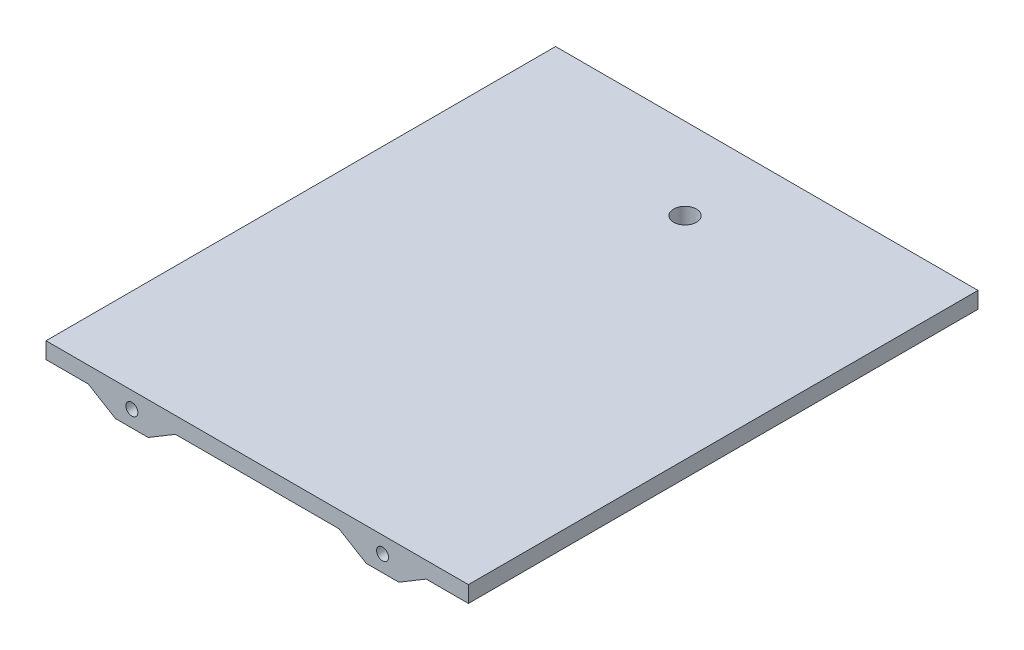
SolidWorks part; units mm, degrees
ref_plane "Płaszczyzna przednia" through (0, 0, 0) normal (0, 0, 1) x (1, 0, 0)
ref_plane "Płaszczyzna górna" through (0, 0, 0) normal (0, 1, 0) x (1, 0, 0)
ref_plane "Płaszczyzna prawa" through (0, 0, 0) normal (1, 0, 0) x (0, 0, -1)
sketch "Szkic15" plane through (0, 0, 0) normal (0, 1, 0) x (1, 0, 0)
  line L0 (-38.75, 69.3124) -> (38.75, 69.3124)
  line L1 (-38.75, 69.3124) -> (-38.75, -26.1876)
  line L2 (-38.75, -26.1876) -> (-52, -43.75)
  line L3 (38.75, 69.3124) -> (38.75, -26.1876)
  line L4 (38.75, -26.1876) -> (52, -43.75)
  line L5 (52, -74.75) -> (52, -43.75)
  line L6 (-60, -74.75) -> (60, -74.75)
  line L7 (-52, -43.75) -> (-52, -74.75)
  line L8 (35.7524, -27.1876) -> (38.75, -26.1876)
  line L9 (-38.75, -26.1876) -> (-35.75, -27.1876)
  line L10 (-35.75, -27.1876) -> (35.7524, -27.1876)
  line L11 (-38.75, -24.1876) -> (38.75, -24.1876)
  point P14 (0, 0)
  point P15 (0, 0)
  point P16 (0, 0)
  point P17 (0, 0)
  point P18 (0, 0)
  point P19 (0, 0)
  dimension "D1" = 3
  dimension "D3" = 77.5
  dimension "D4" = 22
  dimension "D5" = 31
  dimension "D6" = 93.5
  dimension "D7" = 2
  dimension "D8" = 2
  dimension "D9" = 3.16
  dimension "D10" = 3.1623
extrude "Dodanie-wyciągnięcie12" add sketch "Szkic15" along normal blind 3 contours L1 L11 L3 L0 region at (0, 0, -22.5624)
sketch "Szkic17" plane through (0, 0, 0) normal (0, -1, 0) x (1, 0, 0)
  line L1 (-4.5, -49.8124) -> (4.5, -49.8124)
  line L2 (-4.5, -49.8124) -> (-4.5, -58.8124)
  line L3 (-4.5, -58.8124) -> (4.5, -58.8124)
  line L4 (4.5, -49.8124) -> (4.5, -58.8124)
  line L5 (-15, -9.3124) -> (15, -9.3124)
  line L6 (-15, -9.3124) -> (-15, -39.3124)
  line L8 (15, -9.3124) -> (15, -39.3124)
  line L9 (-30, -39.3124) -> (-15, -39.3124)
  line L10 (-30, -39.3124) -> (-30, -69.3124)
  line L11 (-30, -69.3124) -> (-18.1323, -69.3124)
  line L12 (30, -39.3124) -> (30, -69.3124)
  line L13 (15, -69.3124) -> (30, -69.3124)
  line L15 (15, -39.3124) -> (30, -39.3124)
  line L16 (0, -49.8124) -> (0, 33.7148) construction
  line L17 (0, 33.7148) -> (0, -58.8124) construction
  line L18 (-4.5, -54.3124) -> (-57.4, -54.3124) construction
  line L21 (-18.1323, -69.3124) -> (15, -69.3124)
  line L22 (-38.75, -69.3124) -> (38.75, -69.3124) construction
  line L24 (38.75, -69.3124) -> (38.75, 24.1876) construction
  line L25 (-38.75, -69.3124) -> (-38.75, 24.1876) construction
  point P19 (0, 33.7148)
  dimension "D1" = 30
  dimension "D2" = 9
  dimension "D3" = 30
  dimension "D4" = 15
  dimension "D5" = 30
extrude "Dodanie-wyciągnięcie15" add sketch "Szkic17" along normal blind 3
sketch "Szkic18" plane through (0, -3, 0) normal (0, -1, 0) x (1, 0, 0)
  line L12 (-15, -9.3124) -> (-15, -39.3124)
  line L13 (-15, -39.3124) -> (-30, -39.3124)
  line L14 (-30, -39.3124) -> (-30, -69.3124)
  line L15 (-30, -69.3124) -> (30, -69.3124)
  line L20 (30, -69.3124) -> (30, -39.3124)
  line L21 (30, -39.3124) -> (15, -39.3124)
  line L22 (15, -39.3124) -> (15, -9.3124)
  line L23 (15, -9.3124) -> (-15, -9.3124)
  line L24 (-15, -9.3124) -> (-15, -39.3124)
  line L25 (-15, -39.3124) -> (-30, -39.3124)
  line L26 (-30, -39.3124) -> (-30, -69.3124)
  line L27 (-30, -69.3124) -> (30, -69.3124)
  line L32 (30, -69.3124) -> (30, -39.3124)
  line L33 (30, -39.3124) -> (15, -39.3124)
  line L34 (15, -39.3124) -> (15, -9.3124)
  line L35 (15, -9.3124) -> (-15, -9.3124)
  dimension "D1" = 0
extrude "Dodanie-wyciągnięcie16" add sketch "Szkic18" along normal blind 3
sketch "Szkic22" plane through (0, 3, 0) normal (0, 1, 0) x (1, 0, 0)
  line L4 (-4.5, 49.8124) -> (4.5, 49.8124)
  line L5 (4.5, 49.8124) -> (4.5, 58.8124)
  line L6 (4.5, 58.8124) -> (-4.5, 58.8124)
  line L7 (-4.5, 58.8124) -> (-4.5, 49.8124)
  line L8 (-4.5, 49.8124) -> (4.5, 49.8124)
  line L9 (4.5, 49.8124) -> (4.5, 58.8124)
  line L10 (4.5, 58.8124) -> (-4.5, 58.8124)
  line L11 (-4.5, 58.8124) -> (-4.5, 49.8124)
  line L18 (15, 69.3124) -> (-18.1323, 69.3124)
  line L19 (15, 69.3124) -> (-18.1323, 69.3124)
  line L23 (30, 69.3124) -> (15, 69.3124)
  line L24 (30, 39.3124) -> (30, 69.3124)
  line L25 (15, 39.3124) -> (30, 39.3124)
  line L26 (15, 9.3124) -> (15, 39.3124)
  line L27 (-15, 9.3124) -> (15, 9.3124)
  line L28 (-15, 39.3124) -> (-15, 9.3124)
  line L29 (-30, 39.3124) -> (-15, 39.3124)
  line L30 (-30, 69.3124) -> (-30, 39.3124)
  line L31 (-18.1323, 69.3124) -> (-30, 69.3124)
  line L35 (30, 69.3124) -> (15, 69.3124)
  line L36 (30, 39.3124) -> (30, 69.3124)
  line L37 (15, 39.3124) -> (30, 39.3124)
  line L38 (15, 9.3124) -> (15, 39.3124)
  line L39 (-15, 9.3124) -> (15, 9.3124)
  line L40 (-15, 39.3124) -> (-15, 9.3124)
  line L41 (-30, 39.3124) -> (-15, 39.3124)
  line L42 (-30, 69.3124) -> (-30, 39.3124)
  line L43 (-18.1323, 69.3124) -> (-30, 69.3124)
  circle A0 centre (0, 54.3124) radius 2.1
  point P10 (0, 49.8124)
  point P13 (4.5, 54.3124)
  dimension "D3" = 4.2
  dimension "D1" = 0
  dimension "D2" = 0
extrude "Wytnij-wyciągnięcie10" cut sketch "Szkic22" against normal blind 0.5 contours A0 region at (0, 3, -54.3124)
sketch "Szkic27" plane through (0, 0, 24.1876) normal (0, 0, 1) x (1, 0, 0)
  line L0 (-26, 3) -> (-20, 3)
  line L2 (-26, -3) -> (-20, -3)
  line L4 (-20, -3) -> (-20, 3)
  line L5 (-38.75, 3) -> (-38.75, 0) construction
  line L6 (0, -3) -> (0, 3) construction
  line L7 (-26, 3) -> (-20, 3)
  line L8 (38.75, 3) -> (38.75, 0) construction
  line L9 (-38.75, 3) -> (38.75, 3) construction
  line L10 (-26, 3) -> (-26, -3)
  line L11 (26, 3) -> (26, -3)
  line L12 (26, -3) -> (20, -3)
  line L13 (20, -3) -> (20, 3)
  line L14 (26, 3) -> (20, 3)
  line L15 (-20, -3) -> (-15, 0)
  line L16 (-15, 0) -> (-30, 0) construction
  line L17 (-15, -6) -> (-15, 0) construction
  line L18 (-26, -3) -> (-31, 0)
  line L19 (-38.75, 0) -> (38.75, 0) construction
  line L20 (-23, 0) -> (-23, 8.7476) construction
  line L21 (-23, 8.7476) -> (-23, -6.4896) construction
  line L22 (20, -3) -> (15, 0)
  line L23 (26, -3) -> (31, 0)
  circle A0 centre (-23, 0) radius 1.1
  circle A1 centre (23, 0) radius 1.1
  line M10 (-38.75, 0) -> (38.75, 0)
  dimension "D1" = 3
  dimension "D2" = 2.2
  dimension "D3" = 3
  dimension "D5" = 20
extrude "Dodanie-wyciągnięcie17" add sketch "Szkic27" against normal blind 10 contours A0 L10 L2 L4 M10 | A0 M10 | A1 M10 | A1 L13 L12 L11 M10 | L18 L10 M10 | L4 L15 M10 | L22 L13 M10 | L11 L23 M10 region at (18.3333, -1, 24.1876) region at (-23, -1.622, 24.1876) region at (-27.6667, -1, 24.1876) region at (-18.3333, -1, 24.1876) region at (-23, -0.4669, 24.1876) region at (23, -1.622, 24.1876) region at (27.6667, -1, 24.1876) region at (23, -0.4669, 24.1876)
extrude "Wytnij-wyciągnięcie12" cut sketch "Szkic27<5>" against normal up to surface (10 mm away) contours A0 M10 | A0 M10 | A1 M10 | A1 M10 region at (-23, -0.4669, 24.1876) region at (-23, 0.4669, 24.1876) region at (23, -0.4669, 24.1876) region at (23, 0.4669, 24.1876) up to face at (23, -1.5, 14.1876)
sketch "Szkic27<5>" plane through (0, 0, 24.1876) normal (0, 0, 1) x (1, 0, 0) same geometry as "Szkic27"
sketch "Szkic29" plane through (0, 2.5, 0) normal (0, 1, 0) x (1, 0, 0)
  circle A1 centre (0, 54.3124) radius 2.1
  circle A2 centre (0, 54.3124) radius 2.1
  dimension "D1" = 0
extrude "Wytnij-wyciągnięcie13" cut sketch "Szkic29" against normal blind 10
sketch "Szkic30" plane through (0, 0, -39.3124) normal (0, 0, 1) x (1, 0, 0)
  line L0 (15, -6) -> (30, 0)
  line L1 (-15, -6) -> (-30, 0)
  line L2 (-15, -6) -> (-30, -6)
  line L3 (-30, -6) -> (-30, 0)
  line L12 (15, -6) -> (30, -6)
  line L21 (30, -6) -> (30, 0)
extrude "Wytnij-wyciągnięcie14" cut sketch "Szkic30" against normal up to surface (30 mm away) up to face at (0, -0.75, -69.3124)
sketch "Szkic31" plane through (-15, 0, 0) normal (-1, 0, 0) x (0, 0, 1)
  line L0 (-39.3124, -6) -> (-9.3124, 0)
  line L4 (-9.3124, 0) -> (-39.3124, 0)
  line L5 (-39.3124, 0) -> (-39.3124, -6)
  line L6 (-39.3124, -6) -> (-9.3124, -6)
  line L7 (-9.3124, -6) -> (-9.3124, 0)
  line L10 (-39.3124, -6) -> (-9.3124, -6)
  line L11 (-9.3124, -6) -> (-9.3124, 0)
  dimension "D1" = 0
extrude "Wytnij-wyciągnięcie15" cut sketch "Szkic31" against normal up to surface (30 mm away) contours L10 L11 L0 up to face at (15, -3, -24.3124)
sketch "Szkic32" plane through (0, 0, -69.3124) normal (0, 0, -1) x (-1, 0, 0)
  line L0 (-20, -3) -> (-15, 0) construction
  line L1 (26, -3) -> (31, 0) construction
  line L2 (-20, -3) -> (-20, 3) construction
  line L3 (-26, 3) -> (-20, 3) construction
  line L4 (-26, 3) -> (-26, -3) construction
  line L5 (-26, -3) -> (-20, -3) construction
  line L6 (-26, -3) -> (-31, 0) construction
  line L7 (20, -3) -> (15, 0) construction
  line L8 (26, -3) -> (20, -3) construction
  line L9 (20, -3) -> (20, 3) construction
  line L10 (26, 3) -> (26, -3) construction
  line L11 (26, 3) -> (20, 3) construction
  line L12 (26, 3) -> (20, 3) construction
  line L13 (-20, -3) -> (-15, 0)
  line L14 (26, -3) -> (31, 0)
  line L15 (-20, -3) -> (-20, 3)
  line L16 (-26, 3) -> (-20, 3)
  line L17 (-26, 3) -> (-26, -3)
  line L18 (-26, -3) -> (-20, -3)
  line L19 (-26, -3) -> (-31, 0)
  line L20 (20, -3) -> (15, 0)
  line L21 (26, -3) -> (20, -3)
  line L22 (20, -3) -> (20, 3)
  line L23 (26, 3) -> (26, -3)
  line L24 (26, 3) -> (20, 3)
  line L25 (26, 3) -> (20, 3)
  circle A1 centre (-23, 0) radius 1.1
  circle A2 centre (-23, 0) radius 1.1
  circle A3 centre (23, 0) radius 1.1
  circle A4 centre (23, 0) radius 1.1
  line M3 (-30, 0) -> (-15, -6)
  line M5 (15, -6) -> (30, 0)
  line M6 (30, 0) -> (38.75, 0)
  line M10 (-38.75, 0) -> (-30, 0)
  dimension "D1" = 0
  dimension "D2" = 0
extrude "Dodanie-wyciągnięcie18" add sketch "Szkic32" against normal blind 10 contours L19 L17 M3 M10 | L17 L18 M3 | L23 L21 M5 | L23 L14 M5 M6 region at (-27.9147, -1.3473, -69.3124) region at (-24.8333, -2.5333, -69.3124) region at (24.8333, -2.5333, -69.3124) region at (27.9147, -1.3473, -69.3124)
extrude "Wytnij-wyciągnięcie16" cut sketch "Szkic32<3>" against normal blind 10 contours A2 | A4 region at (23, 0, -69.3124) region at (-23, 0, -69.3124)
sketch "Szkic32<3>" plane through (0, 0, -69.3124) normal (0, 0, -1) x (-1, 0, 0) same geometry as "Szkic32"
